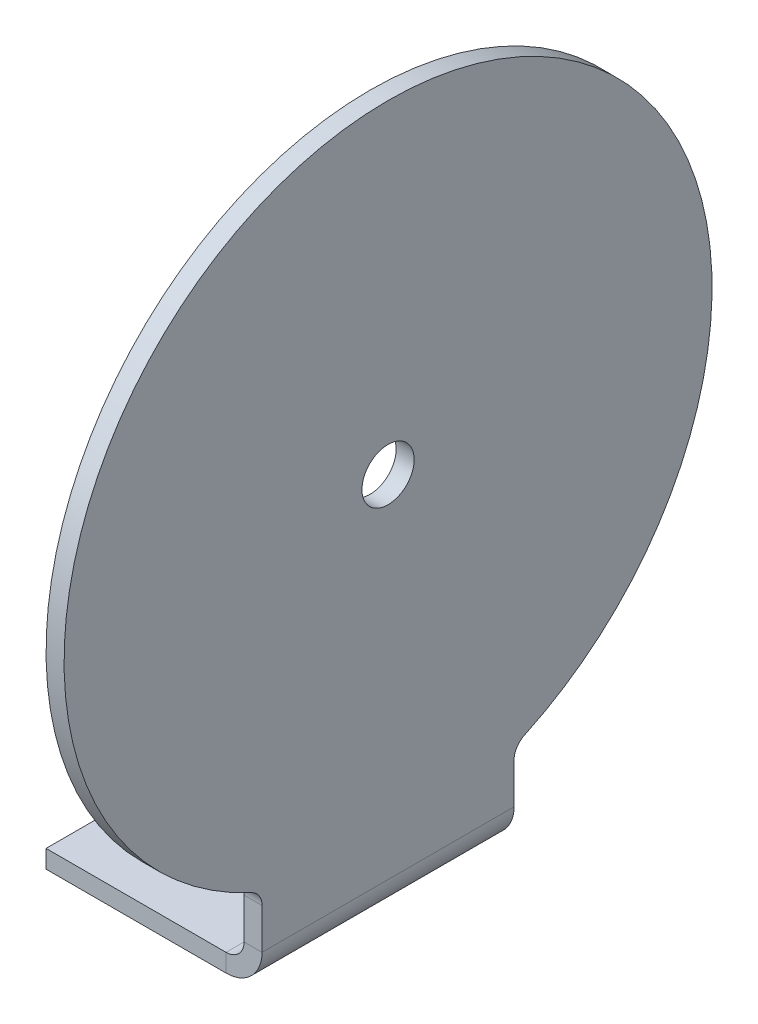
SolidWorks part; units mm, degrees
note: The reader was unsure of these and kept them because the rebuilt part matched: flange length of "Aresta-Flange1".
ref_plane "Plano frontal" through (0, 0, 0) normal (0, 0, 1) x (1, 0, 0)
ref_plane "Plano superior" through (0, 0, 0) normal (0, 1, 0) x (1, 0, 0)
ref_plane "Plano direito" through (0, 0, 0) normal (1, 0, 0) x (0, 0, -1)
sketch "Esboço1" plane through (0, 0, 0) normal (0, 1, 0) x (1, 0, 0)
  line L1 (-30, -35) -> (30, -35)
  line L2 (-30, -35) -> (-30, 35)
  line L3 (-30, 35) -> (30, 35)
  line L4 (30, -35) -> (30, 35)
  line L5 (-30, -35) -> (30, 35) construction
  line L6 (-30, 35) -> (30, -35) construction
  point P0 (0, 0)
  dimension "D1" = 60
  dimension "D2" = 70
base flange "Flange-base1" sketch "Esboço1" thickness 5 reverse thickness direction no parameters "D1"=10
edge flange "Aresta-Flange1" sketch "Esboço8" flange angle 90 flange length 91 flange position material inside bend radius 5 thickness 5 relief rectangular parameters "D6"=10
sketch "Esboço8" plane through (30, 0, 0) normal (1, 0, 0) x (0, 0, -1)
  line L0 (-35, 0) -> (35, 0) construction
  line L1 (-35, 0) -> (35, 0)
  line L2 (-35, 0) -> (-35, 86)
  line L3 (-35, 86) -> (35, 86)
  line L4 (35, 86) -> (35, 0)
bend "DobradeAresta1" bend radius 5 bend angle 90 parameters "D5"=1
sketch "Esboço9" plane through (30, 0, 0) normal (1, 0, 0) x (0, 0, -1)
  circle A0 centre (0, 102.425) radius 90
base flange "Aba1" sketch "Esboço9" thickness 5 reverse thickness direction no parameters "D1"=10
fillet "Filete5" radius 5 1 edges at (27.5, 19.5094, -35)
fillet "Filete6" radius 5 1 edges at (27.5, 19.5094, 35)
sketch "Esboço10" plane through (30, 0, 0) normal (1, 0, 0) x (0, 0, -1)
  circle A4 centre (0, 102.425) radius 7.25
extrude "Corte-extrusão1" cut sketch "Esboço10" against normal blind 5 normal cut yes
sketch "Curva-Linhas1" [suppressed] plane through (0, 0, 0) normal (0, 1, 0) x (1, 0, 0)
sketch "Caixa delimitadora1" [suppressed] plane through (0, 0, 0) normal (0, 1, 0) x (1, 0, 0)
sheet metal parameters "Chapa metálica1" thickness 5 parameters "D1"=10
flat pattern "Padrão-Plano1" [suppressed]
sketch "Curva-Linhas2" plane through (0, 0, 0) normal (0, 1, 0) x (1, 0, 0)
sketch "Caixa delimitadora2" [suppressed] plane through (0, 0, 0) normal (0, 1, 0) x (1, 0, 0)
sheet metal parameters "Chapa metálica2" thickness 5 parameters "D1"=10
flat pattern "Padrão-Plano1"
sketch "Curva-Linhas2" plane through (0, 0, 0) normal (0, 1, 0) x (1, 0, 0)
  line L0 (25.8512, -35) -> (25.8512, 35) construction
  line L1 (25.8512, -35) -> (25.8512, 35) construction
sketch3d "Caixa delimitadora2" [suppressed]
  line L0 (112.7024, 35, 0) -> (-30, 35, 0) construction
  line L1 (112.7024, -35, 0) -> (-30, -35, 0) construction
  line L2 (112.7024, 35, 0) -> (112.7024, -35, 0) construction
  line L3 (-30, 35, 0) -> (-30, -35, 0) construction
bend of the flat pattern "Planificar-<DobradeAresta1>1"
sheet metal parameters "Chapa metálica3" thickness 5 parameters "D1"=10
flat pattern "Padrão-Plano1"
sketch "Curva-Linhas2" plane through (0, 0, 0) normal (0, 1, 0) x (1, 0, 0)
  line L0 (25.8512, -35) -> (25.8512, 35) construction
  line L1 (25.8512, -35) -> (25.8512, 35) construction
sketch3d "Caixa delimitadora2" [suppressed]
  line L0 (219.1274, 90, 0) -> (-30, 90, 0) construction
  line L1 (219.1274, -90, 0) -> (-30, -90, 0) construction
  line L2 (219.1274, 90, 0) -> (219.1274, -90, 0) construction
  line L3 (-30, 90, 0) -> (-30, -90, 0) construction
bend of the flat pattern "Planificar-<DobradeAresta1>1"
sheet metal parameters "Chapa metálica4" thickness 5 parameters "D1"=10
flat pattern "Padrão-Plano1"
sketch "Curva-Linhas2" plane through (0, 0, 0) normal (0, 1, 0) x (1, 0, 0)
  line L0 (25.8512, -35) -> (25.8512, 35) construction
  line L1 (25.8512, -35) -> (25.8512, 35) construction
sketch3d "Caixa delimitadora2" [suppressed]
  line L0 (219.1274, 90, 0) -> (-30, 90, 0) construction
  line L1 (219.1274, -90, 0) -> (-30, -90, 0) construction
  line L2 (219.1274, 90, 0) -> (219.1274, -90, 0) construction
  line L3 (-30, 90, 0) -> (-30, -90, 0) construction
bend of the flat pattern "Planificar-<DobradeAresta1>1"
